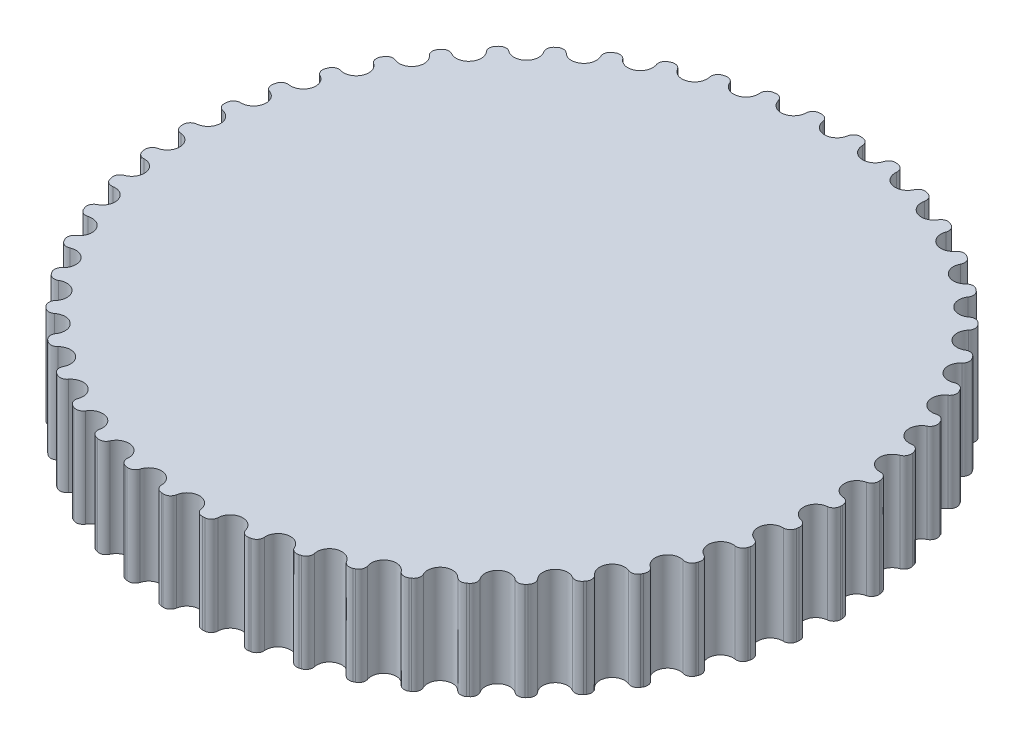
SolidWorks part; units mm, degrees
ref_plane "Front Plane" through (0, 0, 0) normal (0, 0, 1) x (1, 0, 0)
ref_plane "Top Plane" through (0, 0, 0) normal (0, 1, 0) x (1, 0, 0)
ref_plane "Right Plane" through (0, 0, 0) normal (1, 0, 0) x (0, 0, -1)
sketch "Sketch1" plane through (0, 0, 0) normal (0, 1, 0) x (1, 0, 0)
  line L0 (0, 0) -> (0, 23.4921) construction
  line L1 (0, 0) -> (2.903, 22.9795) construction
  circle A0 centre (0, 0) radius 23.4921 construction
  circle A1 centre (0, 0) radius 22.2721 construction
  circle A2 centre (0, 23.1621) radius 0.89 construction
  circle A5 centre (2.903, 22.9795) radius 0.89 construction
  arc A6 (0, 22.2721) -> (0.8797, 23.027) centre (0, 23.1621) ccw
  arc A7 (0.8797, 23.027) -> (1.4038, 23.4501) centre (1.3739, 22.951) cw
  arc A8 (1.5464, 23.4412) -> (2.0133, 22.9556) centre (1.5135, 22.9423) cw
  arc A9 (2.7914, 22.0965) -> (2.0133, 22.9556) centre (2.903, 22.9795) cw
  arc A10 (1.4038, 23.4501) -> (1.5464, 23.4412) centre (0, 0) cw
  arc A11 (0, 22.2721) -> (2.7914, 22.0965) centre (0, 0) ccw
  dimension "D1" = 46.9842
  dimension "D3" = 1.78
  dimension "D4" = 0.5
  dimension "D2" = 1.22
  dimension "D5" = 7.2
extrude "Boss-Extrude1" add sketch "Sketch1" along normal mid plane 7
ref_axis "Axis1" through (0, 3.3, 0) along (0, -1, 0)
pattern_circular "CirPattern1" count 50 over 360 about axis through (0, 3.3, 0) along (0, -1, 0) of "Boss-Extrude1"
equation "\"TEETH_NUM\"= 50"
equation "\"TOOTH_PITCH\"= 3mm"
equation "\"PITCH_LINE_OFFSET\"= .015in"
equation "\"DIAMETER_PER_GROOVE\"= .954925mm"
equation "\"PITCH_DIAMETER\"= \"TEETH_NUM\" * \"DIAMETER_PER_GROOVE\""
equation "\"OUTSIDE_DIAMETER\"= \"PITCH_DIAMETER\" - \"PITCH_LINE_OFFSET\" * 2"
equation "\"D1@Sketch1\"=\"OUTSIDE_DIAMETER\""
equation "\"TOOTH_HEIGHT\"= 1.22mm"
equation "\"D2@Sketch1\"=\"TOOTH_HEIGHT\""
equation "\"TOOTH_DIAMETER\"= 1.78mm"
equation "\"INTERNAL_RADIUS\"= .5mm"
equation "\"D3@Sketch1\"=\"TOOTH_DIAMETER\""
equation "\"D5@Sketch1\"=360 / \"TEETH_NUM\""
equation "\"D4@Sketch1\"=\"INTERNAL_RADIUS\""
equation "\"D1@CirPattern1\"=\"TEETH_NUM\""
equation "\"PULLEY_WIDTH\"= 7mm"
equation "\"D1@Boss-Extrude1\"=\"PULLEY_WIDTH\""
